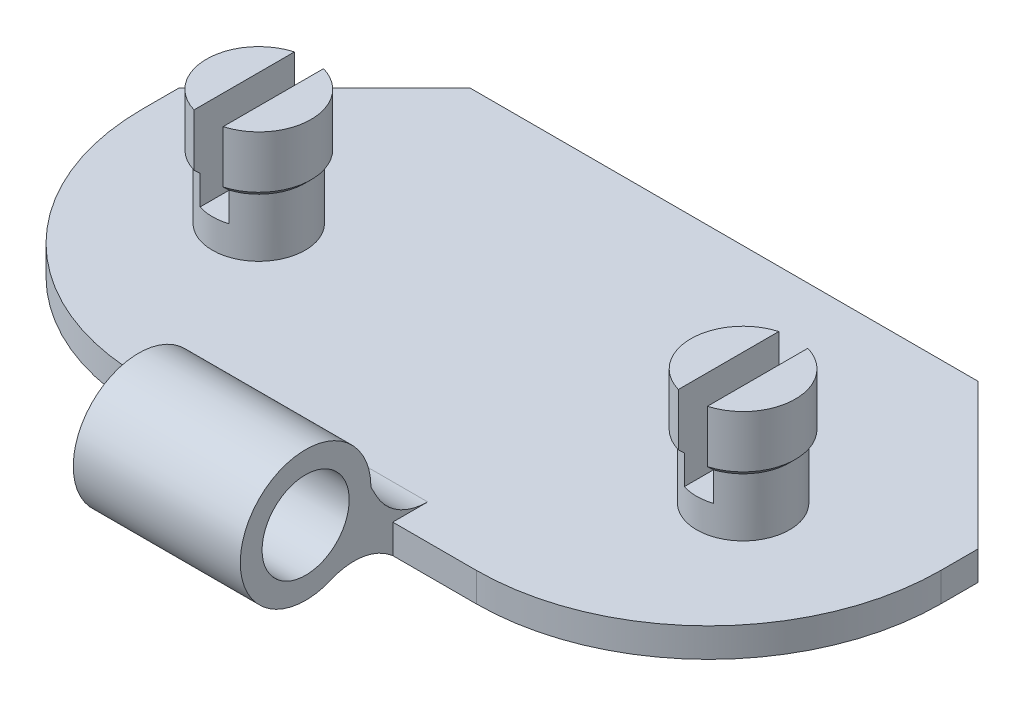
SolidWorks part; units mm, degrees
ref_plane "Front Plane" through (0, 0, 0) normal (0, 0, 1) x (1, 0, 0)
ref_plane "Top Plane" through (0, 0, 0) normal (0, 1, 0) x (1, 0, 0)
ref_plane "Right Plane" through (0, 0, 0) normal (1, 0, 0) x (0, 0, -1)
sketch "Sketch1" plane through (0, 0, 0) normal (0, 1, 0) x (1, 0, 0)
  line L0 (0, 0) -> (0, 11.8039) construction
  line L1 (27.5, -19) -> (-27.5, -19)
  line L2 (27.5, -19) -> (27.5, 19)
  line L3 (27.5, 19) -> (-27.5, 19)
  line L4 (-27.5, -19) -> (-27.5, 19)
  line L5 (27.5, -19) -> (-27.5, 19) construction
  line L6 (27.5, 19) -> (-27.5, -19) construction
  circle A0 centre (-16.675, 3.65) radius 3.4
  circle A1 centre (16.675, 3.65) radius 3.4
  point P0 (0, 0)
  dimension "D3" = 6.8
  dimension "D1" = 55
  dimension "D2" = 38
  dimension "D4" = 15.35
  dimension "D5" = 16.675
sketch "Sketch2" plane through (0, 0, 0) normal (0, 1, 0) x (1, 0, 0)
  line L1 (27.5, -19) -> (-27.5, -19)
  line L2 (27.5, -19) -> (27.5, 19)
  line L3 (27.5, 19) -> (-27.5, 19)
  line L4 (-27.5, -19) -> (-27.5, 19)
  line L5 (27.5, -19) -> (-27.5, 19) construction
  line L6 (27.5, 19) -> (-27.5, -19) construction
  point P0 (0, 0)
  dimension "D1" = 38
extrude "Boss-Extrude1" add sketch "Sketch2" along normal blind 2
sketch "Sketch3" plane through (0, 0, 0) normal (0, 1, 0) x (1, 0, 0)
  line L0 (0, 0) -> (0, 14.4604) construction
  circle A0 centre (-16.675, 3.65) radius 3.2
  circle A2 centre (16.675, 3.65) radius 3.2
extrude "Boss-Extrude2" add sketch "Sketch3" along normal blind 10
sketch "Sketch4" plane through (0, 10, 0) normal (0, 1, 0) x (1, 0, 0)
  line L0 (-16.675, 6.85) -> (-16.675, 0.45) construction
  line L1 (0, -1.1) -> (0, 1.1) construction
  circle A0 centre (-16.675, 3.65) radius 3.2 construction
  circle A1 centre (-16.675, 3.65) radius 3.2 construction
  circle A2 centre (-16.675, 3.65) radius 3.6
  circle A3 centre (16.675, 3.65) radius 3.6
extrude "Boss-Extrude3" add sketch "Sketch4" against normal blind 1
chamfer "Chamfer1" distance 3 angle 45 2 edges at (16.675, 9, -6.85) (-16.675, 9, -0.45)
sketch "Sketch5" plane through (0, 10, 0) normal (0, 1, 0) x (1, 0, 0)
  line L0 (16.675, 7.25) -> (16.675, 0.05) construction
  line L1 (0, -1.1) -> (0, 1.1) construction
  line L2 (17.675, -1.6922) -> (15.675, -1.6922)
  line L3 (17.675, -1.6922) -> (17.675, 8.9922)
  line L4 (17.675, 8.9922) -> (15.675, 8.9922)
  line L5 (15.675, -1.6922) -> (15.675, 8.9922)
  line L6 (17.675, -1.6922) -> (15.675, 8.9922) construction
  line L7 (17.675, 8.9922) -> (15.675, -1.6922) construction
  line L8 (-17.675, 8.9922) -> (-15.675, 8.9922)
  line L9 (-15.675, -1.6922) -> (-15.675, 8.9922)
  line L10 (-17.675, -1.6922) -> (-15.675, -1.6922)
  line L11 (-17.675, -1.6922) -> (-17.675, 8.9922)
  circle A0 centre (16.675, 3.65) radius 3.6 construction
  point P4 (16.675, 3.65)
extrude "Cut-Extrude1" cut sketch "Sketch5" against normal blind 6
chamfer "Chamfer2" distance 10 angle 45 2 edges at (27.5, 1, -19) (-27.5, 1, -19)
ref_plane "Plane3" through (0, 0, 0) normal (-1, 0, 0) x (0, 0, 1)
sketch "Sketch6" plane through (0, 0, 0) normal (-1, 0, 0) x (0, 0, 1)
  line L0 (19, 2) -> (15.55, 4.8284) construction
  line L1 (11.05, 4.8284) -> (9.55, 2)
  line L2 (-9, 2) -> (19, 2) construction
  line L3 (9.55, 2) -> (12.05, 2)
  line L4 (-0.45, 2) -> (-0.45, 4) construction
  circle A0 centre (15.55, 4.8284) radius 3
  arc A1 (12.05, 2) -> (11.05, 4.8284) centre (15.55, 4.8284) ccw
  circle A2 centre (15.55, 4.8284) radius 4.5 construction
  dimension "D1" = 1.5
  dimension "D2" = 6
  dimension "D3" = 9
  dimension "D4" = 6
  dimension "D5" = 16
sketch "Sketch8" plane through (0, 0, 0) normal (-1, 0, 0) x (0, 0, 1)
  line L1 (9.55, 2) -> (19, 2)
  line L2 (9.55, 2) -> (9.55, 0)
  line L3 (9.55, 0) -> (19, 0)
  line L4 (19, 2) -> (19, 0)
extrude "Cut-Extrude2" cut sketch "Sketch8" against normal through all and the other way through all
sketch "Sketch9" plane through (0, 0, 0) normal (-1, 0, 0) x (0, 0, 1)
  line L0 (9.55, 2) -> (11.05, 4.8284)
  line L1 (9.55, 0) -> (12.05, 2)
  line L2 (9.55, 2) -> (9.55, 0)
  circle A0 centre (15.55, 4.8284) radius 3
  arc A1 (12.05, 2) -> (11.05, 4.8284) centre (15.55, 4.8284) ccw
extrude "Boss-Extrude4" add sketch "Sketch9" along normal mid plane 11.5
fillet "Fillet1" radius 4 2 edges at (0, 2, 12.05) (0, 2, 9.55)
fillet "Fillet2" radius 16 2 edges at (-27.5, 1, 9.55) (27.5, 1, 9.55)
